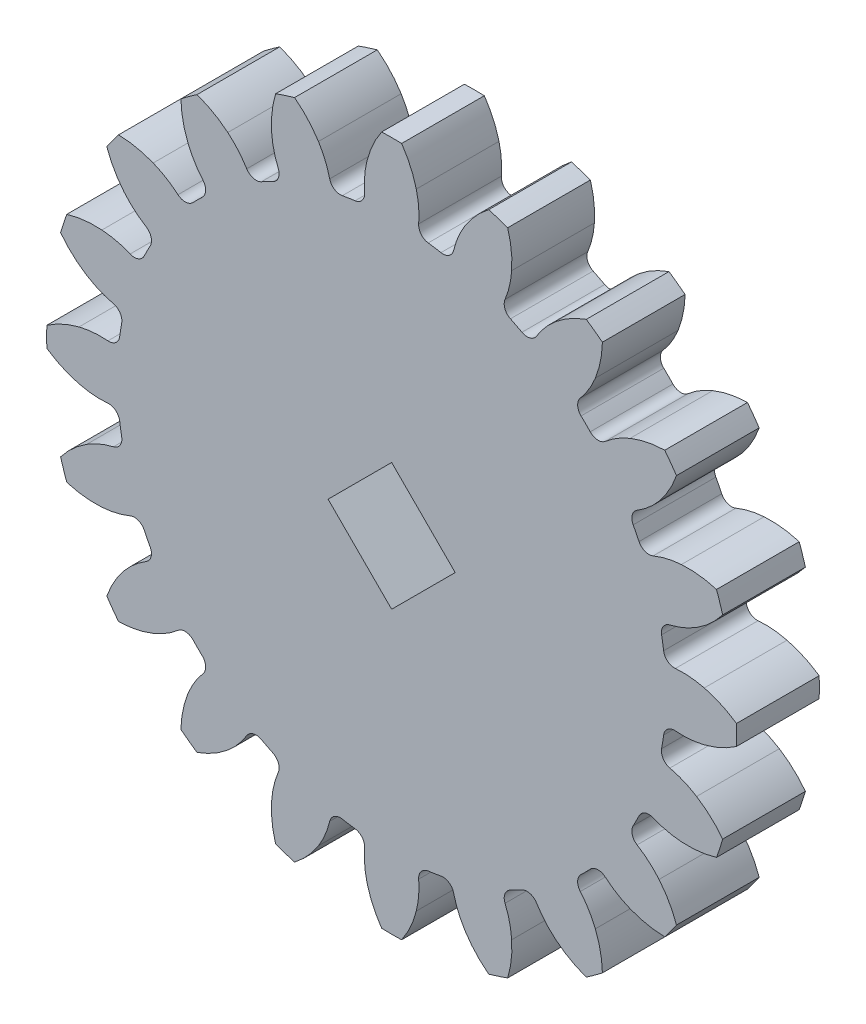
SolidWorks part; units mm, degrees
ref_plane "Front" through (0, 0, 0) normal (0, 0, 1) x (1, 0, 0)
ref_plane "Top" through (0, 0, 0) normal (0, 1, 0) x (1, 0, 0)
ref_plane "Right" through (0, 0, 0) normal (1, 0, 0) x (0, 0, -1)
sketch "Sketch1" plane through (0, 0, 0) normal (0, 0, 1) x (1, 0, 0)
  line L0 (0, 0) -> (22.1544, 0) construction
  line L1 (22.1544, 0) -> (24.3699, 0) construction
  circle A0 centre (0, 0) radius 22.1544 construction
  circle A1 centre (0, 0) radius 24.3699
  dimension "pitch_diameter" = 44.3089
  dimension "addendum" = 2.2154
extrude "GEAR_BASE" add sketch "Sketch1" along normal mid plane 5.842
sketch "Sketch2" plane through (0, 0, 2.921) normal (0, 0, 1) x (1, 0, 0)
  line L0 (0, 0) -> (19.3851, 0) construction
  line L1 (19.3851, 0) -> (22.1544, 0) construction
  line L2 (0, 0) -> (-24.3699, 0) construction
  line L3 (0, 0) -> (-23.1771, -7.5307) construction
  line L4 (-23.3851, -6.8577) -> (-21.5428, -5.1699) construction
  line L5 (-21.5428, -5.1699) -> (-18.9476, -4.0952) construction
  line L6 (-24.3597, -0.7043) -> (-22.086, -1.7402) construction
  line L7 (-22.086, -1.7402) -> (-19.2858, -1.9604) construction
  line L8 (-21.005, -6.8249) -> (-21.5428, -5.1699) construction
  line L9 (-22.086, -1.7402) -> (-22.086, 0) construction
  line L12 (0, 0) -> (-22.086, -1.7402) construction
  line L13 (0, 0) -> (-21.5428, -5.1699) construction
  line L14 (-21.5428, -5.1699) -> (-19.1736, -15.042) construction
  line L15 (-22.086, -1.7402) -> (-22.8835, 8.3808) construction
  line L16 (-21.5428, -5.1699) -> (-22.086, -1.7402) construction
  line L17 (-19.1465, -3.0325) -> (-19.2858, -1.9604) construction
  line L18 (-19.1465, -3.0325) -> (-18.9476, -4.0952) construction
  circle A0 centre (0, 0) radius 22.1544 construction
  circle A1 centre (0, 0) radius 19.3851 construction
  circle A2 centre (0, 0) radius 24.3699 construction
  arc A3 (-23.3851, -6.8577) -> (-24.3597, -0.7043) centre (0, 0) cw
  arc A4 (-18.9476, -4.0952) -> (-19.2858, -1.9604) centre (0, 0) cw construction
  arc A6 (-23.3851, -6.8577) -> (-21.5428, -5.1699) centre (-17.838, -11.063) cw
  arc A7 (-24.3597, -0.7043) -> (-22.086, -1.7402) centre (-20.3836, 5.0093) ccw
  arc A8 (-21.5428, -5.1699) -> (-19.653, -4.3767) centre (-18.199, -10.4888) cw
  arc A9 (-22.086, -1.7402) -> (-20.0436, -1.9106) centre (-20.5495, 4.3516) ccw
  arc A10 (-19.653, -4.3767) -> (-19.0697, -3.483) centre (-19.8324, -3.6224) ccw
  arc A11 (-20.0436, -1.9106) -> (-19.2126, -2.5803) centre (-19.9812, -2.6835) cw
  arc A12 (-19.0697, -3.483) -> (-19.2126, -2.5803) centre (0, 0) cw
  dimension "base_fillet" = 0.7754
  dimension "D12" = 6.9609
  dimension "deddendum" = 2.7693
  dimension "D3" = 18
  dimension "D4" = 1.7402
  dimension "D5" = 1.7402
  dimension "D11" = 3.4724
  dimension "Pressure_Angle" = 20
  dimension "D14" = 9
  dimension "D15" = 9
extrude "GEAR_CUT" cut sketch "Sketch2" against normal through all
ref_axis "GEAR_AXIS" through (0, 0, 50) along (0, 0, -1)
pattern_circular "GEAR_TEETH" count 20 over 360 about axis through (0, 0, 50) along (0, 0, -1) of "GEAR_CUT"
sketch "Sketch9" plane through (0, 0, -2.921) normal (0, 0, -1) x (-1, 0, 0)
  line L0 (0, -4.4901) -> (4.4901, 0)
  line L1 (4.4901, 0) -> (0, 4.4901)
  line L2 (0, 4.4901) -> (-4.4901, 0)
  line L3 (-4.4901, 0) -> (0, -4.4901)
  circle A0 centre (0, 0) radius 4.4901
  dimension "D1" = 8.9803
extrude "Cut-Extrude2" cut sketch "Sketch9" against normal through all contours L2 L3 L0 L1 region at (0, 0, -2.921)
equation "\"N_teeth\"= 20"
equation "\"pitch_diameter\"= 20/11.464968 "
equation "\"Pd\"=\"N_teeth\"/\"pitch_diameter\""
equation "\"addendum\"=1.000/\"Pd\""
equation "\"face_width\"=0.23"
equation "\"deddendum\"=1.250/\"Pd\""
equation "\"D3@Sketch2\" = 360/\"N_teeth\""
equation "\"tooth_thickness\"=1.571/\"Pd\""
equation "\"D4@Sketch2\" = \"tooth_thickness\"/2"
equation "\"D5@Sketch2\" = \"tooth_thickness\"/2"
equation "\"Pressure_Angle\"=20.000000"
equation "\"base_fillet\"=0.35/\"Pd\""
equation "\"D12@Sketch2\" = 2*\"tooth_thickness\""
equation "\"hub_diameter\"=1.57"
equation "\"bore\"=6.35"
equation "\"hub_projection\"=0.250000"
equation "\"sss_diam\"=0.062500"
